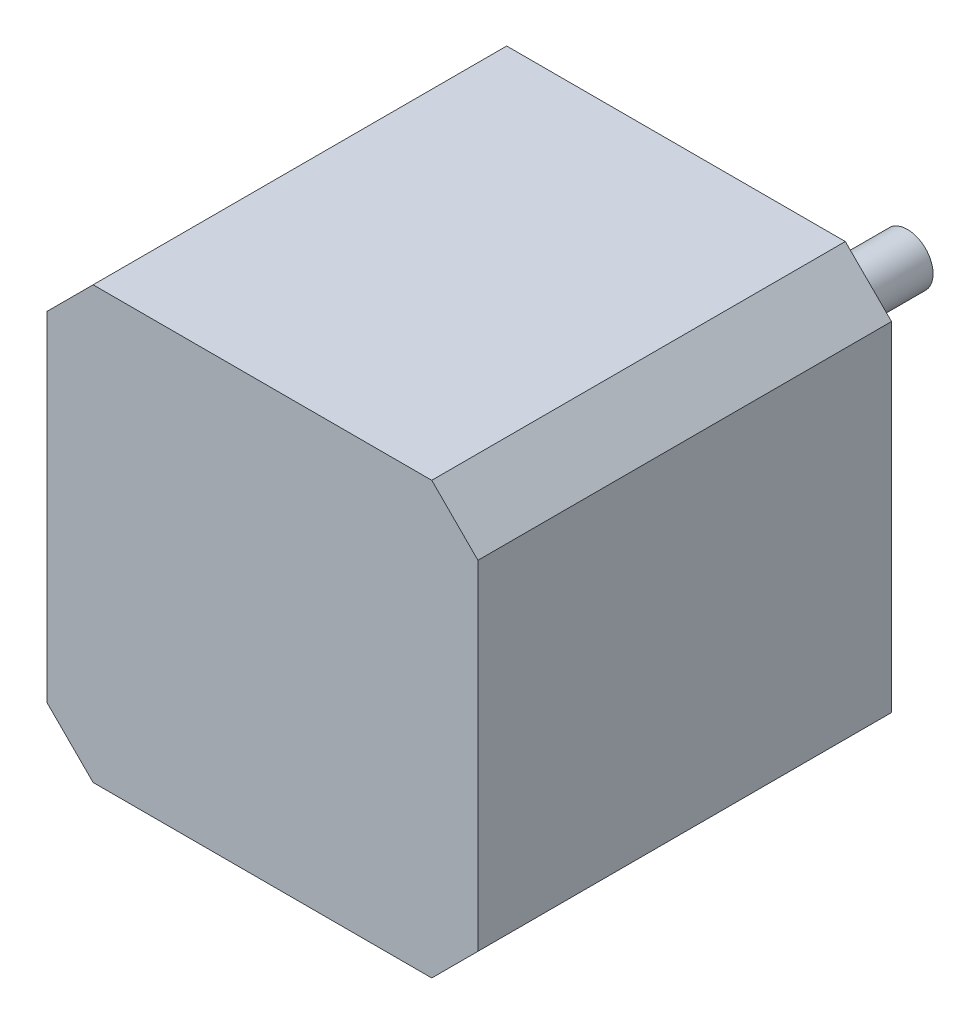
SolidWorks part; units mm, degrees
ref_plane "Front Plane" through (0, 0, 0) normal (0, 0, 1) x (1, 0, 0)
ref_plane "Top Plane" through (0, 0, 0) normal (0, 1, 0) x (1, 0, 0)
ref_plane "Right Plane" through (0, 0, 0) normal (1, 0, 0) x (0, 0, -1)
sketch "Sketch1" plane through (0, 0, 0) normal (0, 0, 1) x (1, 0, 0)
  line L1 (-21, -21) -> (21, -21)
  line L2 (-21, -21) -> (-21, 21)
  line L3 (-21, 21) -> (21, 21)
  line L4 (21, -21) -> (21, 21)
  line L5 (-21, -21) -> (21, 21) construction
  line L6 (-21, 21) -> (21, -21) construction
  line L7 (-15.5, -15.5) -> (15.5, -15.5) construction
  line L8 (-15.5, -15.5) -> (-15.5, 15.5) construction
  line L9 (-15.5, 15.5) -> (15.5, 15.5) construction
  line L10 (15.5, -15.5) -> (15.5, 15.5) construction
  line L11 (-15.5, -15.5) -> (15.5, 15.5) construction
  line L12 (-15.5, 15.5) -> (15.5, -15.5) construction
  circle A0 centre (0, 0) radius 11
  circle A1 centre (15.5, 15.5) radius 1.5
  circle A2 centre (15.5, -15.5) radius 1.5
  circle A3 centre (-15.5, -15.5) radius 1.5
  circle A4 centre (-15.5, 15.5) radius 1.5
  point P0 (0, 0)
  point P22 (0, 0)
  dimension "D3" = 22
  dimension "D6" = 3
  dimension "D1" = 42
  dimension "D2" = 42
  dimension "D4" = 31
  dimension "D5" = 31
  dimension "D7" = 4
extrude "Boss-Extrude1" add sketch "Sketch1" along normal blind 40.3 contours A2 | A3 | L1 L4 L3 L2 A4 A3 A2 A1 A0 | A0 | A4 | A1 region at (-20.406, 0, 0) region at (0, 0, 0) region at (15.5, 15.5, 0) region at (15.5, -15.5, 0) region at (-15.5, -15.5, 0) region at (-15.5, 15.5, 0)
extrude "Cut-Extrude1" cut sketch "Sketch1<3>" along normal blind 5 contours A1 | A4 | A2 | A3 region at (15.5, 15.5, 0) region at (15.5, -15.5, 0) region at (-15.5, -15.5, 0) region at (-15.5, 15.5, 0)
sketch "Sketch1<3>" plane through (0, 0, 0) normal (0, 0, 1) x (1, 0, 0) same geometry as "Sketch1"
extrude "Boss-Extrude2" add sketch "Sketch1<4>" against normal blind 1.8 contours A0 region at (0, 0, 0)
sketch "Sketch1<4>" plane through (0, 0, 0) normal (0, 0, 1) x (1, 0, 0) same geometry as "Sketch1"
chamfer "Chamfer1" distance 4.5 angle 45 4 edges at (21, 21, 20.15) (21, -21, 20.15) (-21, -21, 20.15) (-21, 21, 20.15)
sketch "Sketch2" plane through (0, 0, -1.8) normal (0, 0, -1) x (-1, 0, 0)
  circle A0 centre (0, 0) radius 2.5
  dimension "D1" = 5
extrude "Boss-Extrude3" add sketch "Sketch2" along normal blind 20.75
